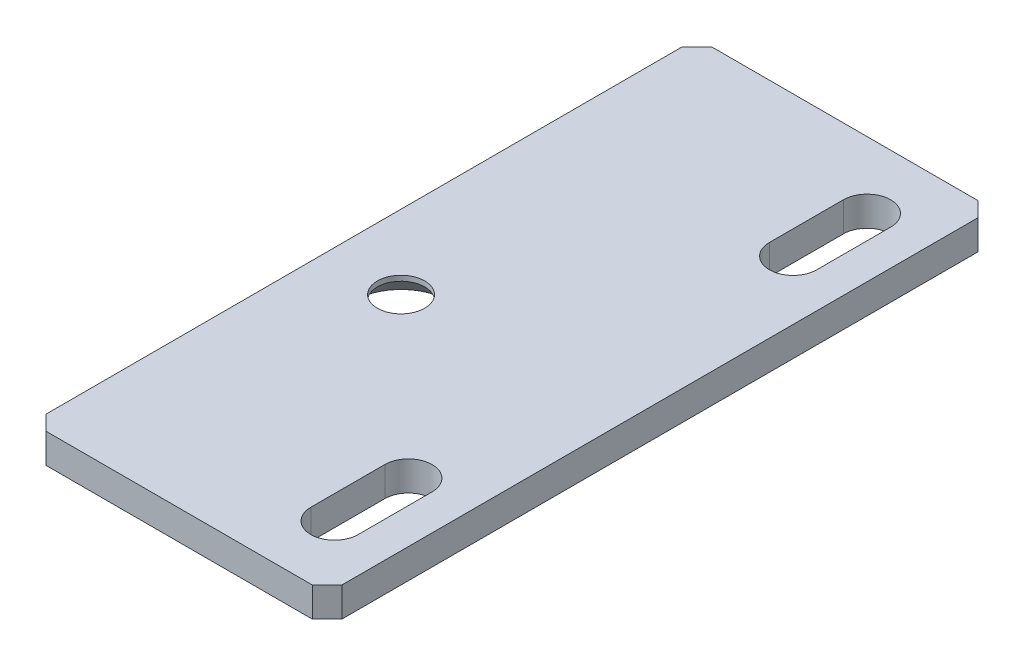
SolidWorks part; units mm, degrees
material "6061 Alloy"
ref_plane "Front Plane" through (0, 0, 0) normal (0, 0, 1) x (1, 0, 0)
ref_plane "Top Plane" through (0, 0, 0) normal (0, 1, 0) x (1, 0, 0)
ref_plane "Right Plane" through (0, 0, 0) normal (1, 0, 0) x (0, 0, -1)
sketch "Sketch1" plane through (0, 0, 0) normal (0, 1, 0) x (1, 0, 0)
  line L5 (10, -22.5) -> (-10, -22.5)
  line L6 (10, -22.5) -> (10, 22.5)
  line L7 (10, 22.5) -> (-10, 22.5)
  line L8 (-10, -22.5) -> (-10, 22.5)
  line L9 (10, -22.5) -> (-10, 22.5) construction
  line L10 (10, 22.5) -> (-10, -22.5) construction
  point P0 (0, 0)
  dimension "D3" = 20
  dimension "D4" = 45
extrude "Base" add sketch "Sketch1" along normal blind 2
sketch "Sketch6" plane through (0, 2, 0) normal (0, 1, 0) x (1, 0, 0)
  line L0 (6, 18) -> (6, 13) construction
  line L1 (7.6, 18) -> (7.6, 13)
  line L2 (4.4, 18) -> (4.4, 13)
  line L3 (6, -13) -> (6, -18) construction
  line L4 (7.6, -13) -> (7.6, -18)
  line L5 (4.4, -13) -> (4.4, -18)
  line L6 (0, 0) -> (-4.8321, 0) construction
  line L7 (10, -22.5) -> (10, 22.5) construction
  line L8 (10, 22.5) -> (-10, 22.5) construction
  arc A0 (7.6, 18) -> (4.4, 18) centre (6, 18) ccw
  arc A1 (4.4, 13) -> (7.6, 13) centre (6, 13) ccw
  arc A2 (7.6, -13) -> (4.4, -13) centre (6, -13) ccw
  arc A3 (4.4, -18) -> (7.6, -18) centre (6, -18) ccw
  point P3 (6, 15.5)
  point P8 (6, -15.5)
  dimension "D1" = 3.2
  dimension "D2" = 5
  dimension "D3" = 31
  dimension "D4" = 4
  dimension "D5" = 4.5
extrude "ScrewSlots" cut sketch "Sketch6" against normal through all
hole_wizard "PulleyHole" positions "Sketch4" profile "Sketch5" countersink size "M3" standard "ANSI Metric" end condition through all
sketch "Sketch4" plane through (0, 0, 0) normal (0, -1, 0) x (-1, 0, 0)
  line L2 (-10, -22.5) -> (-10, 22.5) construction
  line L4 (-10, 22.5) -> (10, 22.5) construction
  point P0 (5, -2.5)
  dimension "D1" = 25
  dimension "D2" = 15
sketch "Sketch5" plane through (-5, 0, 2.5) normal (1, 0, 0) x (0, 0, -1)
  line L0 (0, 0) -> (0, 2)
  line L1 (0, 2) -> (1.6, 2)
  line L2 (1.6, 2) -> (1.6, 1.65)
  line L3 (1.6, 1.65) -> (3.25, 0)
  line L5 (3.25, 0) -> (0, 0)
  line L6 (-1.6, 1.65) -> (-3.25, 0) construction
  line L11 (0, -6.35) -> (0, 107.95) construction
  dimension "Thru Hole Dia." = 3.2
  dimension "Thru Hole Depth" = 2
  dimension "Near C'Sink Dia." = 6.5
  dimension "Near C'Sink Angle" = 90
chamfer "Chamfer1" distance 1 angle 45 4 edges at (-10, 1, -22.5) (10, 1, -22.5) (10, 1, 22.5) (-10, 1, 22.5)
